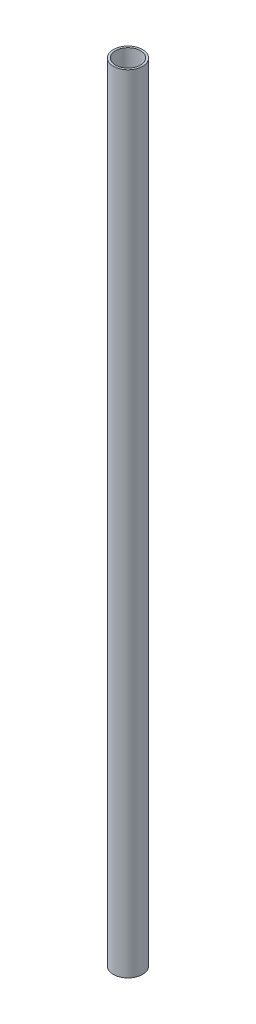
SolidWorks part; units mm, degrees
ref_plane "Front Plane" through (0, 0, 0) normal (0, 0, 1) x (1, 0, 0)
ref_plane "Top Plane" through (0, 0, 0) normal (0, 1, 0) x (1, 0, 0)
ref_plane "Right Plane" through (0, 0, 0) normal (1, 0, 0) x (0, 0, -1)
sketch "Sketch1" plane through (0, 0, 0) normal (0, 1, 0) x (1, 0, 0)
  circle A0 centre (0, 0) radius 12.7
  circle A1 centre (0, 0) radius 10.922
extrude "Boss-Extrude2" add sketch "Sketch1" along normal blind 685.8
